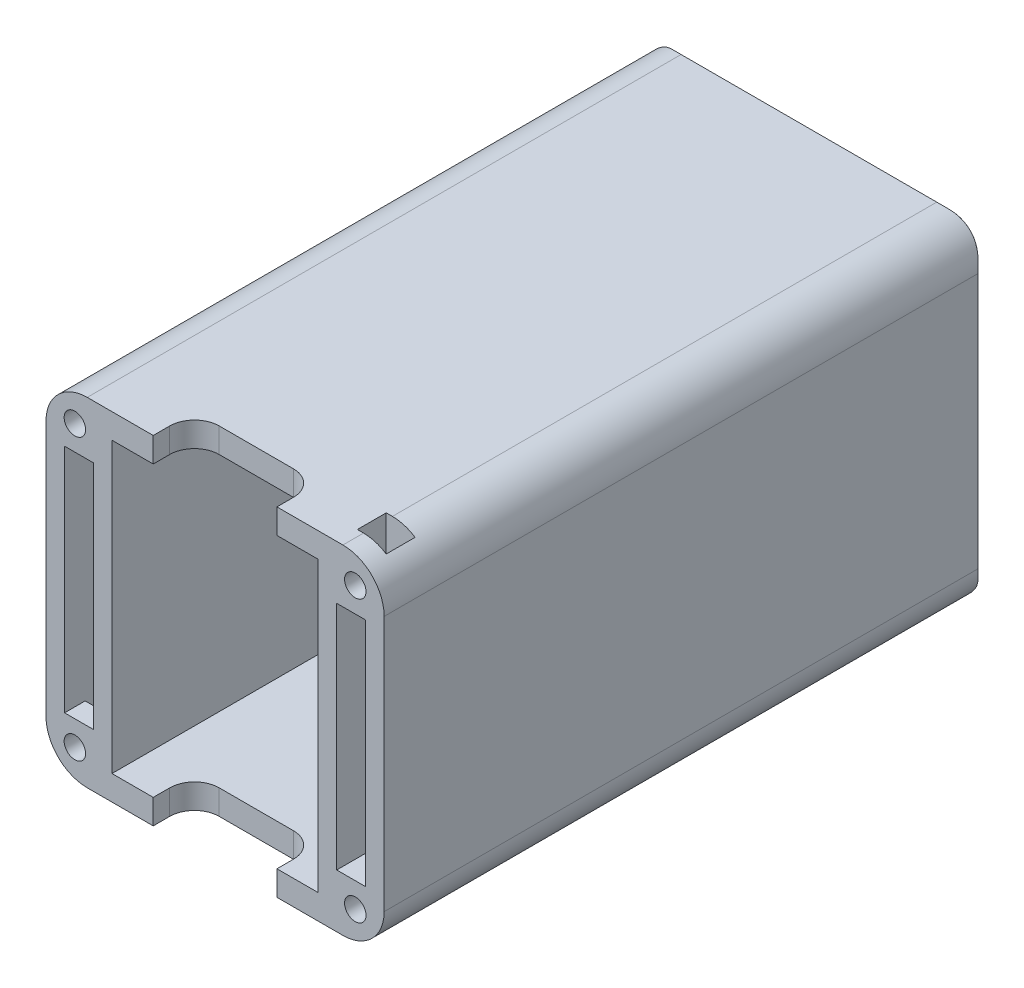
SolidWorks part; units mm, degrees
ref_plane "Front" through (0, 0, 0) normal (0, 0, 1) x (1, 0, 0)
ref_plane "Top" through (0, 0, 0) normal (0, 1, 0) x (1, 0, 0)
ref_plane "Right" through (0, 0, 0) normal (1, 0, 0) x (0, 0, -1)
sketch "ｽｹｯﾁ1" plane through (0, 0, 0) normal (0, 0, 1) x (1, 0, 0)
  line L1 (20.5, -20.5) -> (-20.5, -20.5)
  line L2 (20.5, -20.5) -> (20.5, 20.5)
  line L3 (20.5, 20.5) -> (-20.5, 20.5)
  line L4 (-20.5, -20.5) -> (-20.5, 20.5)
  line L5 (20.5, -20.5) -> (-20.5, 20.5) construction
  line L6 (20.5, 20.5) -> (-20.5, -20.5) construction
  line L7 (12.5, -17.5) -> (-12.5, -17.5)
  line L8 (12.5, -17.5) -> (12.5, 17.5)
  line L9 (12.5, 17.5) -> (-12.5, 17.5)
  line L10 (-12.5, -17.5) -> (-12.5, 17.5)
  line L11 (12.5, -17.5) -> (-12.5, 17.5) construction
  line L12 (12.5, 17.5) -> (-12.5, -17.5) construction
  point P0 (0, 0)
  point P6 (0, 0)
  dimension "D1" = 41
  dimension "D2" = 35
  dimension "D3" = 25
extrude "ﾎﾞｽ - 押し出し1" add sketch "ｽｹｯﾁ1" along normal blind 72
sketch "ｽｹｯﾁ2" plane through (0, 0, 0) normal (0, 0, -1) x (-1, 0, 0)
  line L1 (20.5, -20.5) -> (-20.5, -20.5)
  line L2 (20.5, -20.5) -> (20.5, 20.5)
  line L3 (20.5, 20.5) -> (-20.5, 20.5)
  line L4 (-20.5, -20.5) -> (-20.5, 20.5)
  line L5 (20.5, -20.5) -> (-20.5, 20.5) construction
  line L6 (20.5, 20.5) -> (-20.5, -20.5) construction
  point P0 (0, 0)
extrude "ﾎﾞｽ - 押し出し2" add sketch "ｽｹｯﾁ2" along normal blind 3
chamfer "面取り1" distance 3 angle 45 4 edges at (0, 20.5, -3) (-20.5, 0, -3) (0, -20.5, -3) (20.5, 0, -3)
fillet "ﾌｨﾚｯﾄ1" radius 5 8 edges at (-20.5, -20.5, 36) (20.5, -20.5, 36) (20.5, 20.5, 36) (-20.5, 20.5, 36) (19, -19, -1.5) (-19, -19, -1.5) (-19, 19, -1.5) (19, 19, -1.5)
sketch "ｽｹｯﾁ3" plane through (0, 0, 72) normal (0, 0, 1) x (1, 0, 0)
  line L1 (-7.5, 17.5) -> (7.5, 17.5)
  line L2 (-7.5, 17.5) -> (-7.5, 20.5)
  line L3 (-7.5, 20.5) -> (7.5, 20.5)
  line L4 (7.5, 17.5) -> (7.5, 20.5)
  line L6 (15.5, 20.5) -> (-15.5, 20.5) construction
  line L7 (12.5, 17.5) -> (-12.5, 17.5) construction
  point P4 (0, 17.5)
  dimension "D1" = 15
extrude "ｶｯﾄ - 押し出し1" cut sketch "ｽｹｯﾁ3" against normal blind 5
fillet "ﾌｨﾚｯﾄ2" radius 3 2 edges at (7.5, 19, 67) (-7.5, 19, 67)
sketch "ｽｹｯﾁ4" plane through (0, 0, 72) normal (0, 0, 1) x (1, 0, 0)
  line L1 (-14.75, 14) -> (-18.25, 14)
  line L2 (-14.75, 14) -> (-14.75, -14)
  line L3 (-14.75, -14) -> (-18.25, -14)
  line L4 (-18.25, 14) -> (-18.25, -14)
  line L6 (14.75, 14) -> (18.25, 14)
  line L7 (14.75, 14) -> (14.75, -14)
  line L8 (14.75, -14) -> (18.25, -14)
  line L9 (18.25, 14) -> (18.25, -14)
  line L10 (12.5, -17.5) -> (12.5, 17.5) construction
  line L11 (-12.5, 17.5) -> (-12.5, -17.5) construction
  dimension "D1" = 3.5
  dimension "D2" = 28
  dimension "D3" = 14
  dimension "D4" = 2.25
  dimension "D5" = 2.25
extrude "ｶｯﾄ - 押し出し2" cut sketch "ｽｹｯﾁ4" against normal blind 6
sketch "ｽｹｯﾁ6" plane through (0, 14, 0) normal (0, -1, 0) x (1, 0, 0)
  line L0 (18.25, 66) -> (18.25, 72) construction
  line L1 (14.75, 66) -> (18.25, 66)
  line L2 (14.75, 66) -> (14.75, 69.5)
  line L3 (14.75, 69.5) -> (18.25, 69.5)
  line L4 (18.25, 66) -> (18.25, 69.5)
extrude "ｶｯﾄ - 押し出し4" cut sketch "ｽｹｯﾁ6" against normal through all
sketch "ｽｹｯﾁ7" plane through (0, -14, 0) normal (0, 1, 0) x (1, 0, 0)
  line L1 (-18.25, -66) -> (-14.75, -66)
  line L2 (-18.25, -66) -> (-18.25, -69.5)
  line L3 (-18.25, -69.5) -> (-14.75, -69.5)
  line L4 (-14.75, -66) -> (-14.75, -69.5)
  line L5 (-14.75, -66) -> (-14.75, -72) construction
extrude "ｶｯﾄ - 押し出し5" cut sketch "ｽｹｯﾁ7" against normal through all
mirror "ﾐﾗｰ1" about plane through (0, 0, 0) normal (0, 1, 0) of "ﾌｨﾚｯﾄ2", "ｶｯﾄ - 押し出し1"
sketch "ｽｹｯﾁ8" plane through (0, 0, 72) normal (0, 0, 1) x (1, 0, 0)
  circle A0 centre (17, 17) radius 1.3
  circle A1 centre (17, -17) radius 1.3
  circle A2 centre (-17, -17) radius 1.3
  circle A3 centre (-17, 17) radius 1.3
  dimension "D1" = 2.6
extrude "ｶｯﾄ - 押し出し6" cut sketch "ｽｹｯﾁ8" against normal up to surface (2.5 mm away) up to face at (-16.3121, -17.7755, 69.5)
